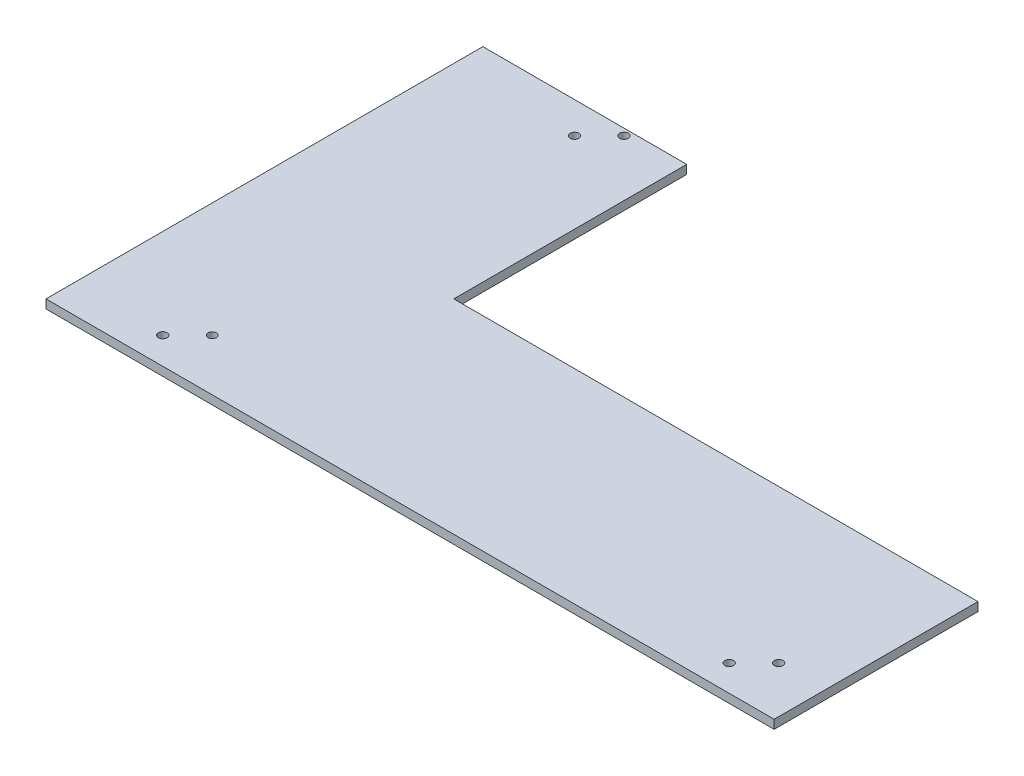
SolidWorks part; units mm, degrees
ref_plane "Front Plane" through (0, 0, 0) normal (0, 0, 1) x (1, 0, 0)
ref_plane "Top Plane" through (0, 0, 0) normal (0, 1, 0) x (1, 0, 0)
ref_plane "Right Plane" through (0, 0, 0) normal (1, 0, 0) x (0, 0, -1)
sketch "Sketch1" plane through (0, 0, 0) normal (0, 1, 0) x (1, 0, 0)
  line L0 (-125, -35) -> (125, -35)
  line L2 (-125, -35) -> (-125, 35)
  line L4 (125, -35) -> (125, 35)
  line L5 (-125, -35) -> (125, 35) construction
  line L6 (-125, 35) -> (125, -35) construction
  line L15 (-55, 35) -> (125, 35)
  line L17 (-125, 35) -> (-125, 115)
  line L18 (-125, 115) -> (-55, 115)
  line L19 (-55, 35) -> (-55, 115)
  circle A0 centre (-94.1332, -25.7565) radius 1.5
  circle A1 centre (-85.6479, -17.2712) radius 1.4446
  circle A2 centre (100.5732, -25.9922) radius 1.5
  circle A3 centre (109.0585, -17.5069) radius 1.5
  circle A4 centre (-82.7607, 104.2435) radius 1.5
  circle A5 centre (-74.2754, 112.7288) radius 1.5
  point P0 (0, 0)
  point P27 (84.6265, -16.469)
  point P28 (66.5424, -17.0576)
  point P30 (58.0571, -25.5429)
  point P32 (-93.1852, -25.7565)
  point P34 (-84.6999, -17.2712)
  point P36 (-81.8127, 104.2435)
  point P38 (-73.3274, 112.7288)
  dimension "D1" = 250
  dimension "D2" = 70
  dimension "D3" = 70
  dimension "D4" = 150
extrude "Boss-Extrude1" add sketch "Sketch1" along normal blind 3
